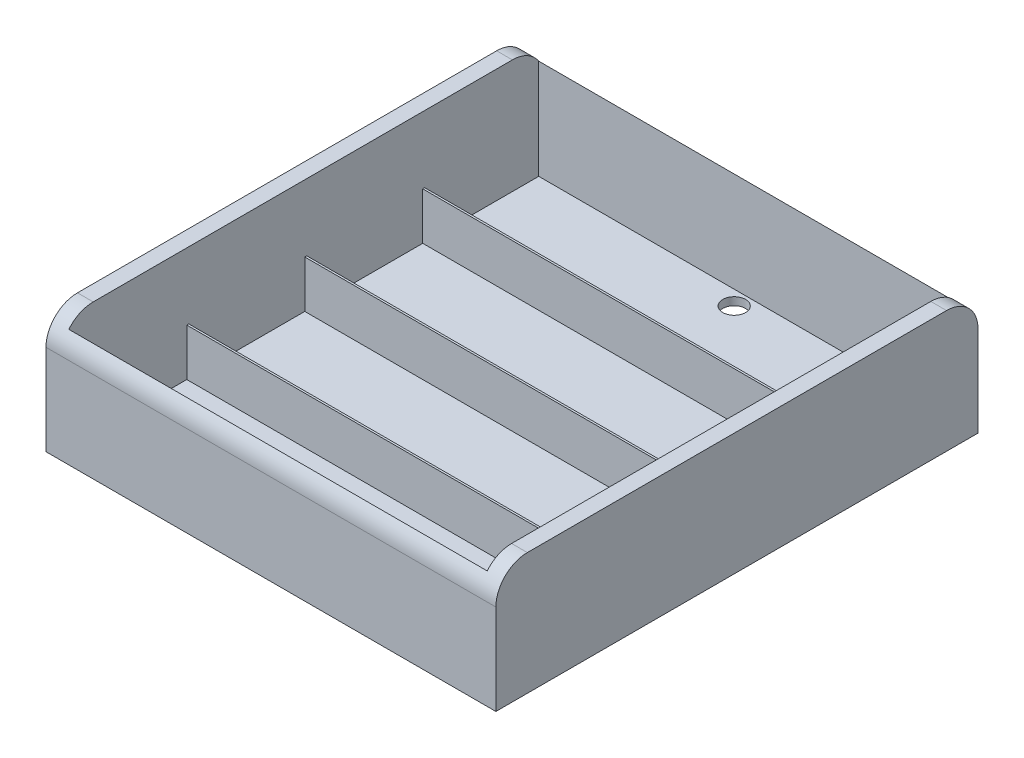
SolidWorks part; units mm, degrees
material "ABS"
ref_plane "Front" through (0, 0, 0) normal (0, 0, 1) x (1, 0, 0)
ref_plane "Top" through (0, 0, 0) normal (0, 1, 0) x (1, 0, 0)
ref_plane "Right" through (0, 0, 0) normal (1, 0, 0) x (0, 0, -1)
sketch "Sketch1" plane through (0, 0, 0) normal (0, 1, 0) x (1, 0, 0)
  line L1 (0, 0) -> (57.2, 0)
  line L2 (0, 0) -> (0, 61.3)
  line L3 (0, 61.3) -> (57.2, 61.3)
  line L4 (57.2, 0) -> (57.2, 61.3)
  dimension "D1" = 57.2
  dimension "D2" = 61.3
extrude "Boss-Extrude1" add sketch "Sketch1" along normal blind 15.5
hole_wizard "Ø2.9 (2.9) Diameter Hole1" positions "Sketch3" profile "Sketch2" hole size "Ø2.9" standard "Ansi Metric" end condition through all
sketch "Sketch3" plane through (0, 15.5, 0) normal (0, 1, 0) x (-1, 0, 0)
  line L0 (-57.2, -61.3) -> (0, -61.3) construction
  line L1 (-57.2, 0) -> (-57.2, -61.3) construction
  point P0 (-28.7, -58.8)
  point P1 (-28.7, -3.7)
  dimension "D1" = 55.1
  dimension "D2" = 2.5
  dimension "D3" = 28.5
  dimension "D4" = 28.5
sketch "Sketch2" plane through (28.7, 15.5, -58.8) normal (1, 0, 0) x (0, 0, 1)
  line L0 (0, 0) -> (0, 15.5)
  line L1 (0, 15.5) -> (1.45, 15.5)
  line L2 (1.45, 15.5) -> (1.45, 0)
  line L5 (1.45, 0) -> (0, 0)
  line L11 (0, -6.35) -> (0, 107.95) construction
  dimension "Thru Hole Dia." = 2.9
  dimension "Thru Hole Depth" = 15.5
sketch "Sketch4" plane through (0, 15.5, 0) normal (0, 1, 0) x (1, 0, 0)
  line L0 (0, 61.3) -> (0, 0) construction
  line L1 (2, 60.65) -> (55.2, 60.65)
  line L2 (2, 60.65) -> (2, 0.9)
  line L3 (2, 0.9) -> (55.2, 0.9)
  line L4 (55.2, 60.65) -> (55.2, 0.9)
  line L5 (57.2, 0) -> (57.2, 61.3) construction
  line L6 (0, 0) -> (57.2, 0) construction
  line L7 (57.2, 61.3) -> (0, 61.3) construction
  dimension "D1" = 2
  dimension "D2" = 2
  dimension "D3" = 0.9
  dimension "D4" = 0.65
extrude "Cut-Extrude1" cut sketch "Sketch4" against normal offset from surface (14.5 mm away) 1 up to face at (28.6, 0, -30.65)
fillet "Fillet4" radius 4 2 edges at (28.6, 15.5, 0) (28.6, 15.5, -61.3)
sketch "Sketch5" plane through (0, 1, 0) normal (0, 1, 0) x (1, 0, 0)
  line L1 (2, 16.15) -> (55.2, 16.15)
  line L2 (2, 16.15) -> (2, 15.9)
  line L3 (2, 15.9) -> (55.2, 15.9)
  line L4 (55.2, 16.15) -> (55.2, 15.9)
  line L5 (2, 60.65) -> (2, 0.9) construction
  line L6 (55.2, 0.9) -> (55.2, 60.65) construction
  line L7 (2, 0.9) -> (55.2, 0.9) construction
  dimension "D1" = 0
  dimension "D2" = 0
  dimension "D3" = 0.25
  dimension "D4" = 15
extrude "Boss-Extrude2" add sketch "Sketch5" along normal blind 6
pattern_linear "LPattern1" count 3 spacing 15 along (0, 0, -1) of "Boss-Extrude2"
